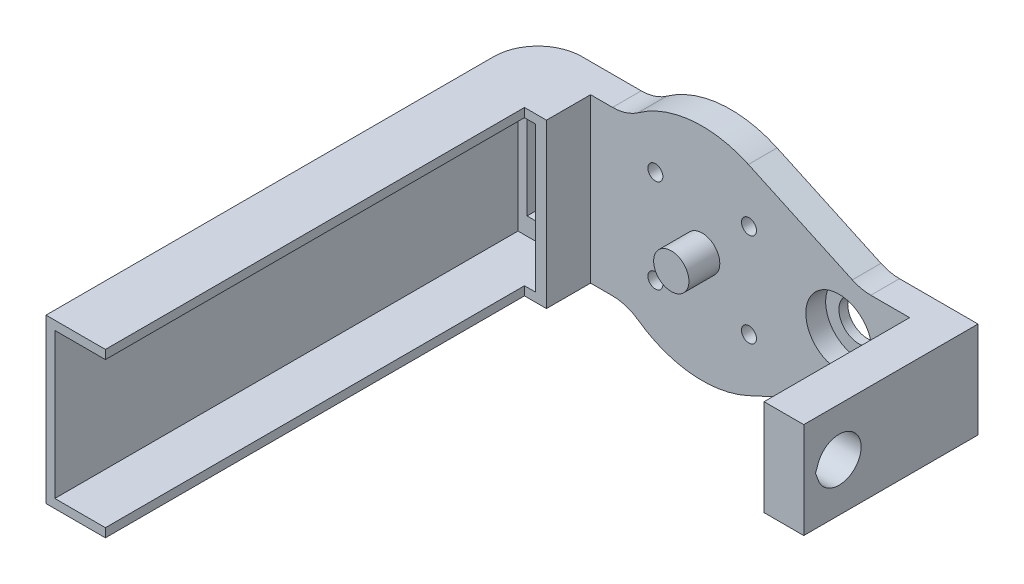
SolidWorks part; units mm, degrees
ref_plane "Front Plane" through (0, 0, 0) normal (0, 0, 1) x (1, 0, 0)
ref_plane "Top Plane" through (0, 0, 0) normal (0, 1, 0) x (1, 0, 0)
ref_plane "Right Plane" through (0, 0, 0) normal (1, 0, 0) x (0, 0, -1)
sketch "Sketch1" plane through (0, 0, 0) normal (0, 0, 1) x (1, 0, 0)
  line L0 (10.4839, 22.6956) -> (36.0323, 10.8939)
  line L1 (36.0323, -10.8939) -> (10.4839, -22.6956)
  circle A0 centre (0, 0) radius 22.215 construction
  circle A1 centre (31, 0) radius 10.2 construction
  arc A2 (10.4839, 22.6956) -> (10.4839, -22.6956) centre (0, 0) ccw
  arc A3 (36.0323, -10.8939) -> (36.0323, 10.8939) centre (31, 0) ccw
  dimension "D1" = 20.4
  dimension "D2" = 44.43
  dimension "D4" = 25
  dimension "D5" = 12
  dimension "D3" = 31
extrude "Boss-Extrude1" add sketch "Sketch1" along normal blind 4.5
sketch "Sketch2" plane through (0, 0, 4.5) normal (0, 0, 1) x (1, 0, 0)
  circle A0 centre (31, 0) radius 7.5
  dimension "D1" = 15
extrude "Cut-Extrude1" cut sketch "Sketch2" against normal through all
sketch "Sketch3" plane through (0, 0, 4.5) normal (0, 0, 1) x (1, 0, 0)
  circle A0 centre (0, 0) radius 4
  dimension "D1" = 8
extrude "Boss-Extrude2" add sketch "Sketch3" along normal blind 7
sketch "Sketch4" plane through (0, 0, 0) normal (0, 0, -1) x (-1, 0, 0)
  line L0 (-36.0323, 10.8939) -> (-56.0323, 10.8939)
  line L1 (-36.0323, -10.8939) -> (-56.0323, -10.8939)
  line L2 (-56.0323, -10.8939) -> (-56.0323, 10.8939)
  line L3 (22.5016, 10.8939) -> (42.5016, 10.8939)
  line L4 (42.5016, 10.8939) -> (42.5016, -10.8939)
  line L5 (42.5016, -10.8939) -> (22.5016, -10.8939)
  arc A0 (-10.4839, -22.6956) -> (-10.4839, 22.6956) centre (0, 0) ccw construction
  arc A1 (22.5016, -10.8939) -> (22.5016, 10.8939) centre (0, 0) ccw
  arc A2 (-36.0323, 10.8939) -> (-36.0323, -10.8939) centre (-31, 0) ccw construction
  arc A3 (-36.0323, 10.8939) -> (-36.0323, -10.8939) centre (-31, 0) ccw
  dimension "D1" = 20
  dimension "D2" = 20
extrude "Boss-Extrude3" add sketch "Sketch4" against normal up to surface (4.5 mm away) up to face at (4, 0, 4.5)
fillet "Fillet1" radius 10 4 edges at (-42.5016, 10.8939, 2.25) (-42.5016, -10.8939, 2.25) (56.0323, -10.8939, 2.25) (56.0323, 10.8939, 2.25)
sketch "Sketch8" plane through (0, 0, 4.5) normal (0, 0, 1) x (1, 0, 0)
  line L0 (56.0323, 0.8939) -> (56.0323, -0.8939) construction
  line L2 (56.0323, 0.8939) -> (56.0323, -0.8939)
  line L3 (55.4014, -4.3896) -> (55.4014, 4.3896)
  line L4 (-42.5016, -0.8939) -> (-42.5016, 0.8939) construction
  line L6 (-42.5016, -0.8939) -> (-42.5016, 0.8939)
  line L7 (-41.8707, 4.3896) -> (-41.8707, -4.3896)
  arc A0 (56.0323, 0.8939) -> (46.0323, 10.8939) centre (46.0323, 0.8939) ccw construction
  arc A1 (46.0323, -10.8939) -> (56.0323, -0.8939) centre (46.0323, -0.8939) ccw construction
  arc A2 (56.0323, 0.8939) -> (55.4014, 4.3896) centre (46.0323, 0.8939) ccw
  arc A3 (55.4014, -4.3896) -> (56.0323, -0.8939) centre (46.0323, -0.8939) ccw
  arc A4 (-32.5016, 10.8939) -> (-42.5016, 0.8939) centre (-32.5016, 0.8939) ccw construction
  arc A5 (-42.5016, -0.8939) -> (-32.5016, -10.8939) centre (-32.5016, -0.8939) ccw construction
  arc A6 (-41.8707, 4.3896) -> (-42.5016, 0.8939) centre (-32.5016, 0.8939) ccw
  arc A7 (-42.5016, -0.8939) -> (-41.8707, -4.3896) centre (-32.5016, -0.8939) ccw
extrude "Cut-Extrude4" cut sketch "Sketch8" against normal through all
sketch "Sketch9" plane through (0, 0, 4.5) normal (0, 0, 1) x (1, 0, 0)
  circle A0 centre (0, 0) radius 15 construction
  circle A1 centre (-10.6066, 10.6066) radius 1
  circle A2 centre (10.6066, 10.6066) radius 1
  circle A3 centre (10.6066, -10.6066) radius 1
  circle A4 centre (-10.6066, -10.6066) radius 1
  point P5 (0, 0)
  point P6 (0, 0)
  point P7 (0, 0)
  point P14 (0, 0)
  dimension "D1" = 30
  dimension "D2" = 2
  dimension "D3" = 4
extrude "Cut-Extrude5" cut sketch "Sketch9" against normal through all
sketch "Sketch10" plane through (0, 0, 4.5) normal (0, 0, 1) x (1, 0, 0)
  circle A0 centre (-10.6066, 10.6066) radius 1.7
  circle A1 centre (10.6066, 10.6066) radius 1.7
  circle A2 centre (10.6066, -10.6066) radius 1.7
  circle A3 centre (-10.6066, -10.6066) radius 1.7
  dimension "D1" = 3.4
extrude "Cut-Extrude6" cut sketch "Sketch10" against normal blind 2.4
sketch "Sketch11" plane through (0, 0, 0) normal (0, 0, -1) x (-1, 0, 0)
  line L0 (-40.9602, 14.6461) -> (-73.6718, 18.9155)
  line L1 (-73.6718, 18.9155) -> (-68.6403, -15.6759)
  line L2 (-68.6403, -15.6759) -> (-41.445, -13.2122)
  arc A0 (-40.9602, 14.6461) -> (-41.445, -13.2122) centre (0, 0) ccw
  dimension "D1" = 87
extrude "Cut-Extrude7" cut sketch "Sketch11" against normal up to surface (4.5 mm away) up to face at (-8.9066, -10.6066, 4.5)
fillet "Fillet2" radius 10 2 edges at (42.1138, -10.8939, 2.25) (42.1138, 10.8939, 2.25)
sketch "Sketch12" plane through (0, 0, 4.5) normal (0, 0, 1) x (1, 0, 0)
  line L0 (-22.5016, 10.8939) -> (-42.5927, 14.8195)
  line L1 (-42.5927, 14.8195) -> (-48.1481, -13.6126)
  line L2 (-48.1481, -13.6126) -> (-27.4273, -14.3153)
  line L3 (-27.4273, -14.3153) -> (-22.5016, -10.8939)
  arc A0 (-22.5016, 10.8939) -> (-22.5016, -10.8939) centre (0, 0) ccw
extrude "Cut-Extrude8" cut sketch "Sketch12" against normal through all
sketch "Sketch23" plane through (0, 0, 0) normal (0, 0, -1) x (-1, 0, 0)
  line L2 (-36.0323, -10.8939) -> (-10.4839, -22.6956)
  line L3 (-10.4839, 22.6956) -> (-36.0323, 10.8939)
  line L4 (-36.0323, -10.8939) -> (-10.4839, -22.6956)
  line L5 (-10.4839, 22.6956) -> (-36.0323, 10.8939)
  circle A0 centre (-10.6066, -10.6066) radius 1 construction
  circle A1 centre (10.6066, -10.6066) radius 1 construction
  circle A2 centre (10.6066, 10.6066) radius 1 construction
  circle A3 centre (-10.6066, 10.6066) radius 1 construction
  arc A4 (-10.4839, -22.6956) -> (-10.4839, 22.6956) centre (0, 0) ccw
  arc A5 (-36.0323, 10.8939) -> (-43.4709, 1.5916) centre (-33.4776, 1.2257) ccw
  arc A6 (-43.4709, 1.5916) -> (-43.4709, -1.5916) centre (0, 0) ccw
  arc A7 (-43.4709, -1.5916) -> (-36.0323, -10.8939) centre (-33.4776, -1.2257) ccw
  arc A8 (-10.4839, -22.6956) -> (-10.4839, 22.6956) centre (0, 0) ccw
  arc A9 (-36.0323, 10.8939) -> (-43.4709, 1.5916) centre (-33.4776, 1.2257) ccw
  arc A10 (-43.4709, 1.5916) -> (-43.4709, -1.5916) centre (0, 0) ccw
  arc A11 (-43.4709, -1.5916) -> (-36.0323, -10.8939) centre (-33.4776, -1.2257) ccw
  circle A12 centre (-10.6066, -10.6066) radius 1
  circle A13 centre (10.6066, -10.6066) radius 1
  circle A14 centre (10.6066, 10.6066) radius 1
  circle A15 centre (-10.6066, 10.6066) radius 1
  circle A16 centre (-31, 0) radius 4.5
  dimension "D2" = 9
  dimension "D1" = 0
extrude "Boss-Extrude6" add sketch "Sketch23" along normal blind 2
sketch "Sketch24" plane through (0, 0, -2) normal (0, 0, -1) x (-1, 0, 0)
  line L0 (-10.6066, 10.6066) -> (10.6066, 10.6066) construction
ref_axis "Axis1" through (10.6066, 10.6066, -2) along (-1, 0, 0)
sketch "Sketch25" plane through (0, 0, -2) normal (0, 0, -1) x (-1, 0, 0)
  line L1 (-36.0323, 10.8939) -> (-56.0323, 10.8939)
  line L3 (-36.0323, -10.8939) -> (-56.0323, -10.8939)
  line L4 (-56.0323, 10.8939) -> (-56.0323, -10.8939)
  arc A0 (-43.4709, -1.5916) -> (-36.0323, -10.8939) centre (-33.4776, -1.2257) ccw construction
  arc A1 (-43.4709, 1.5916) -> (-43.4709, -1.5916) centre (0, 0) ccw construction
  arc A2 (-36.0323, 10.8939) -> (-43.4709, 1.5916) centre (-33.4776, 1.2257) ccw construction
  arc A3 (-43.4709, -1.5916) -> (-36.0323, -10.8939) centre (-33.4776, -1.2257) ccw
  arc A4 (-43.4709, 1.5916) -> (-43.4709, -1.5916) centre (0, 0) ccw
  arc A5 (-36.0323, 10.8939) -> (-43.4709, 1.5916) centre (-33.4776, 1.2257) ccw
  dimension "D1" = 20
extrude "Boss-Extrude7" add sketch "Sketch25" against normal up to surface (6.5 mm away) up to face at (24.5985, 0, 4.5)
sketch "Sketch26" plane through (0, 0, 4.5) normal (0, 0, 1) x (1, 0, 0)
  line L0 (36.0323, 10.8939) -> (56.0323, 10.8939) construction
  line L1 (56.0323, -10.8939) -> (47.0323, -10.8939)
  line L2 (56.0323, -10.8939) -> (56.0323, 10.8939)
  line L3 (56.0323, 10.8939) -> (47.0323, 10.8939)
  line L4 (47.0323, -10.8939) -> (47.0323, 10.8939)
  dimension "D1" = 9
extrude "Boss-Extrude8" add sketch "Sketch26" along normal blind 33
sketch "Sketch27" plane through (56.0323, 0, 0) normal (1, 0, 0) x (0, 0, -1)
  circle A0 centre (-29.5, 0) radius 5
extrude "Cut-Extrude9" cut sketch "Sketch27" against normal up to next
sketch "Sketch28" plane through (0, 0, -2) normal (0, 0, -1) x (-1, 0, 0)
  line L1 (16.8152, 18.5) -> (43.7493, 18.5)
  line L3 (16.8152, -18.5) -> (43.7493, -18.5)
  line L4 (0, 0) -> (47.5, 0) construction
  line L5 (47.5, 0) -> (25.875, 18.5) construction
  line L6 (47.5, 0) -> (31.6196, -18.5) construction
  line L7 (43.7493, -18.5) -> (25, 0) construction
  line L8 (25, 0) -> (43.7493, 18.5) construction
  line L9 (43.7493, 18.5) -> (43.7493, -18.5)
  arc A0 (43.7493, -18.5) -> (43.7493, 18.5) centre (0, 0) ccw construction
  arc A2 (-10.4839, -22.6956) -> (-10.4839, 22.6956) centre (0, 0) ccw construction
  arc A3 (16.8152, -18.5) -> (16.8152, 18.5) centre (0, 0) ccw
  dimension "D1" = 95
  dimension "D3" = 37
extrude "Boss-Extrude9" add sketch "Sketch28" against normal up to surface (6.5 mm away) up to face at (38.5, 0, 4.5)
sketch "Sketch29" plane through (0, 0, 4.5) normal (0, 0, 1) x (1, 0, 0)
  line L0 (-43.7493, 18.5) -> (-30.2822, 18.5)
  line L1 (-43.7493, 18.5) -> (-43.7493, -18.5)
  line L2 (-43.7493, -18.5) -> (-30.2822, -18.5)
  line L3 (-16.8152, -18.5) -> (-43.7493, -18.5) construction
  line L4 (-43.7493, 18.5) -> (-16.8152, 18.5) construction
  line L5 (-41.7493, 16.5) -> (-41.7493, -16.5)
  line L6 (-41.7493, 16.5) -> (-43.7493, 18.5) construction
  line L7 (-41.7493, -16.5) -> (-43.7493, -18.5) construction
  line L8 (-41.7493, 16.5) -> (-30.2822, 16.5)
  line L9 (-30.2822, 16.5) -> (-30.2822, 18.5)
  line L10 (-30.2822, -18.5) -> (-30.2822, -16.5)
  line L11 (-30.2822, -16.5) -> (-41.7493, -16.5)
  dimension "D1" = 33
  dimension "D2" = 2
extrude "Boss-Extrude10" add sketch "Sketch29" along normal blind 105
fillet "Fillet3" radius 10 1 edges at (-43.7493, 0, -2)
fillet "Fillet4" radius 10 4 edges at (36.0323, 10.8939, 1.25) (36.0323, -10.8939, 1.25) (-16.8152, 18.5, 1.25) (-16.8152, -18.5, 1.25)
sketch "Sketch30" plane through (56.0323, 0, 0) normal (1, 0, 0) x (0, 0, -1)
  line L0 (-34.1928, 1.7255) -> (-34.8273, 0)
  line L1 (-34.8273, 0) -> (-34.1928, -1.7255)
  line L2 (-34.5, 0) -> (-34.8273, 0) construction
  circle A0 centre (-29.5, 0) radius 5 construction
  arc A1 (-34.1928, 1.7255) -> (-34.1928, -1.7255) centre (-29.5, 0) ccw
  point P5 (-34.8273, 0)
extrude "Cut-Extrude10" cut sketch "Sketch30" against normal up to surface (9 mm away) up to face at (47.0323, 0, 24.5)
sketch "Sketch31" plane through (0, 0, 4.5) normal (0, 0, 1) x (1, 0, 0)
  line L0 (-39.6877, 12.5) -> (-41.7493, 16.5) construction
  line L1 (-39.6877, 12.5) -> (-35.6877, 12.5)
  line L2 (-39.6877, 12.5) -> (-39.6877, -12.5)
  line L3 (-39.6877, -12.5) -> (-35.6877, -12.5)
  line L4 (-35.6877, 12.5) -> (-35.6877, -12.5)
  line L5 (-39.6877, -12.5) -> (-41.7493, -16.5) construction
  dimension "D1" = 25
  dimension "D2" = 4
  dimension "D3" = 4.5
extrude "Cut-Extrude11" cut sketch "Sketch31" against normal through all
sketch "Sketch32" plane through (0, 0, 4.5) normal (0, 0, 1) x (1, 0, 0)
  line L0 (-30.2822, 18.5) -> (-30.2822, 16.5)
  line L1 (-30.2822, 16.5) -> (-27.7493, 16.5)
  line L2 (-27.7493, 16.5) -> (-27.7493, -16.5)
  line L3 (-27.7493, -16.5) -> (-30.2822, -16.5)
  line L4 (-30.2822, -16.5) -> (-30.2822, -18.5)
  line L5 (-30.2822, -18.5) -> (-25.2992, -18.5)
  line L6 (-20.3162, -18.5) -> (-30.2822, -18.5) construction
  line L7 (-25.2992, -18.5) -> (-25.2992, 18.5)
  line L8 (-30.2822, 18.5) -> (-20.3162, 18.5) construction
  line L9 (-25.2992, 18.5) -> (-30.2822, 18.5)
extrude "Boss-Extrude11" add sketch "Sketch32" along normal blind 10
